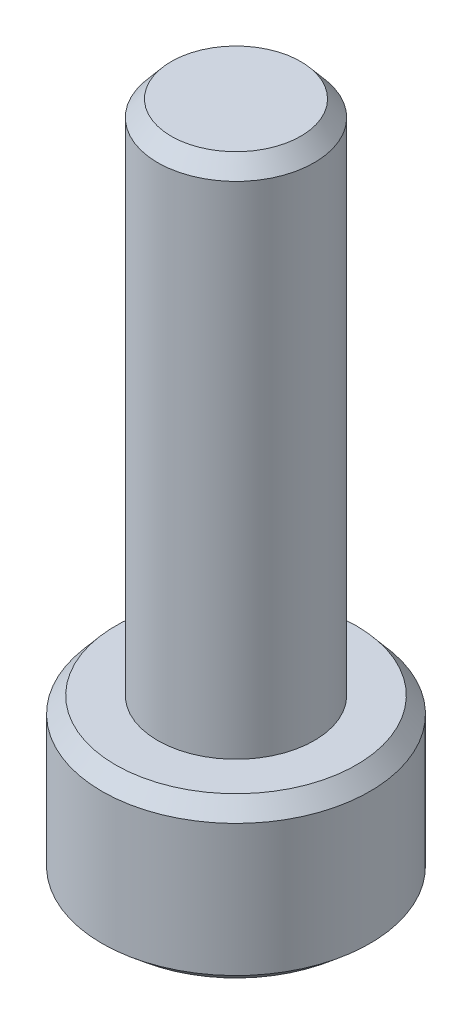
SolidWorks part; units mm, degrees
ref_plane "Front Plane" through (0, 0, 0) normal (0, 0, 1) x (1, 0, 0)
ref_plane "Top Plane" through (0, 0, 0) normal (0, 1, 0) x (1, 0, 0)
ref_plane "Right Plane" through (0, 0, 0) normal (1, 0, 0) x (0, 0, -1)
sketch "Sketch1" plane through (0, 0, 0) normal (0, 1, 0) x (1, 0, 0)
  circle A0 centre (0, 0) radius 4.15
  dimension "D1" = 8.3
extrude "Boss-Extrude1" add sketch "Sketch1" along normal blind 5
sketch "Sketch2" plane through (0, 5, 0) normal (0, 1, 0) x (1, 0, 0)
  circle A0 centre (0, 0) radius 2.425
  dimension "D1" = 4.85
extrude "Boss-Extrude2" add sketch "Sketch2" along normal blind 16
sketch "Sketch3" plane through (0, 0, 0) normal (0, -1, 0) x (1, 0, 0)
  line L1 (0, 2.786) -> (-2.4128, 1.393)
  line L2 (-2.4128, 1.393) -> (-2.4128, -1.393)
  line L3 (-2.4128, -1.393) -> (0, -2.786)
  line L4 (0, -2.786) -> (2.4128, -1.393)
  line L5 (2.4128, -1.393) -> (2.4128, 1.393)
  line L6 (2.4128, 1.393) -> (0, 2.786)
  circle A0 centre (0, 0) radius 2.4128 construction
extrude "Cut-Extrude1" cut sketch "Sketch3" against normal blind 3
chamfer "Chamfer1" distance 0.5 angle 40 3 edges at (0, 0, 4.15) (0, 5, 4.15) (0, 21, 2.425) first distance on face at (0, 0, 0) first distance on face at (0, 5, 4.15) first distance on face at (0, 21, 2.425)
